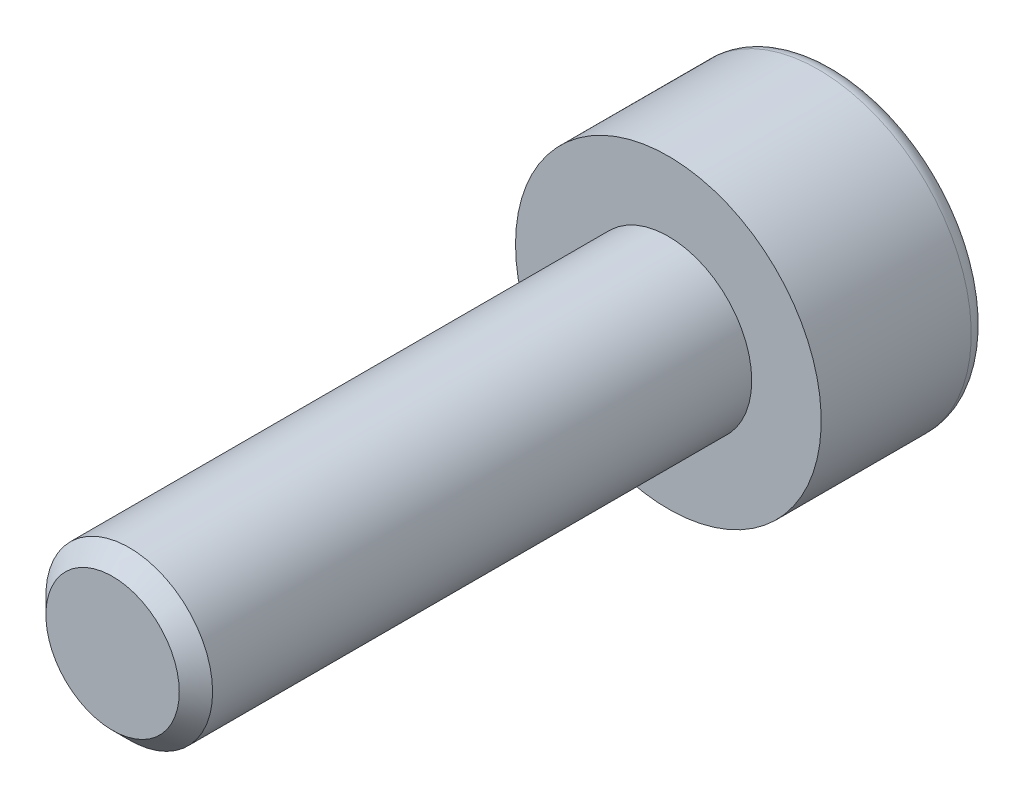
SolidWorks part; units mm, degrees
ref_plane "Plan1" through (0, 0, 0) normal (0, 0, 1) x (1, 0, 0)
ref_plane "Plan2" through (0, 0, 0) normal (0, 1, 0) x (1, 0, 0)
ref_plane "Plan3" through (0, 0, 0) normal (1, 0, 0) x (0, 0, -1)
ref_axis "Z Axis" through (0, 0, -50) along (0, 0, 1)
sketch "Esquisse1" plane through (0, 0, 0) normal (0, 1, 0) x (1, 0, 0)
  line L0 (0, 0) -> (0, 3) construction
  line L1 (0, 0) -> (2.75, 0)
  line L2 (0, 0) -> (0, 3)
  line L3 (0, 3) -> (2.45, 3)
  line L5 (2.75, 0) -> (2.75, 2.7)
  arc A0 (2.45, 3) -> (2.75, 2.7) centre (2.45, 2.7) cw
  dimension "D3" = 0.3
  dimension "D1" = 2.75
  dimension "D2" = 3
revolve "Base-Révolution" add sketch "Esquisse1" angle 360 about L0 reverse direction yes
sketch "Esquisse2" plane through (0, 0, -3) normal (0, 0, 1) x (1, 0, 0)
  line L0 (1.25, -0.7217) -> (1.25, 0.7217)
  line L1 (0, 0) -> (1.25, 0.7217) construction
  line L2 (1, 0) -> (1.25, 0) construction
  line L3 (0, 1.4434) -> (1.25, 0.7217)
  line L4 (0, -1.4434) -> (1.25, -0.7217)
  line L5 (0, 0) -> (0, 1.25) construction
  line L6 (-1.25, -0.7217) -> (-1.25, 0.7217)
  line L7 (0, 1.4434) -> (-1.25, 0.7217)
  line L8 (0, -1.4434) -> (-1.25, -0.7217)
  circle A0 centre (0, 0) radius 1.25 construction
  dimension "D2" = 30
  dimension "D1" = 2.5
extrude "enlev-mat-Extru1" cut sketch "Esquisse2" along normal blind 1.3
sketch "Esquisse3" plane through (0, 0, 0) normal (0, 1, 0) x (1, 0, 0)
  line L1 (0, 0) -> (0, -10) construction
  line L2 (0, 0) -> (1.5, 0)
  line L3 (0, 0) -> (0, -10)
  line L4 (0, -10) -> (1.5, -10)
  line L6 (1.5, 0) -> (1.5, -10)
  dimension "D1" = 10
  dimension "D2" = 1.5
revolve "Boss.-Révol.1" add sketch "Esquisse3" angle 360 about L1 reverse direction yes
cosmetic thread "Représentation de filetage1"
sketch "Esquisse4" plane through (0, 0, 0) normal (0, 1, 0) x (1, 0, 0)
  line L0 (1.195, -10.0305) -> (1.195, -9.9695)
  line L2 (1.195, -9.9695) -> (1.5305, -9.7758)
  line L3 (1.195, -10.0305) -> (1.5305, -10.2242)
  line L4 (1.5305, -9.7758) -> (1.5305, -10.2242)
  line L6 (1.5, 0) -> (1.5, -10) construction
  line L7 (0, -10) -> (1.5, -10) construction
  point P4 (1.5, -10)
  dimension "D2" = 0.0305
  dimension "D3" = 0.0305
  dimension "D4" = 0.3355
  dimension "D5" = 60
  dimension "D1" = 0.305
  dimension "D6" = 60
chamfer "Chanfrein1" distance 0.3 angle 45 1 edges at (1.5, 0, 10)
sketch "Esquisse5" plane through (0, 0, 10) normal (0, 0, 1) x (1, 0, 0)
  circle A0 centre (0, 0) radius 1.5 construction
  circle A1 centre (0, 0) radius 1.5
curve "Hélice1" pitch 0.5 height 9.8 turns 19.6
sweep "Enlèvement de matière-Balayage1" [suppressed] cut profiles "Esquisse4" path "Hélice1"
equation "\"D3@Esquisse1\"=\"D2@Esquisse1\"/10"
equation "\"D1@Chanfrein1\"=\"D2@Esquisse3\"*0.2"
equation "\"D3@Esquisse4\"=0.1*\"D1@Esquisse4\""
equation "\"D4@Esquisse4\"=1.1*\"D1@Esquisse4\""
equation "\"D2@Esquisse4\"=0.1*\"D1@Esquisse4\""
equation "\"D1@Esquisse4\"=0.61*\"D4@Hélice1\""
